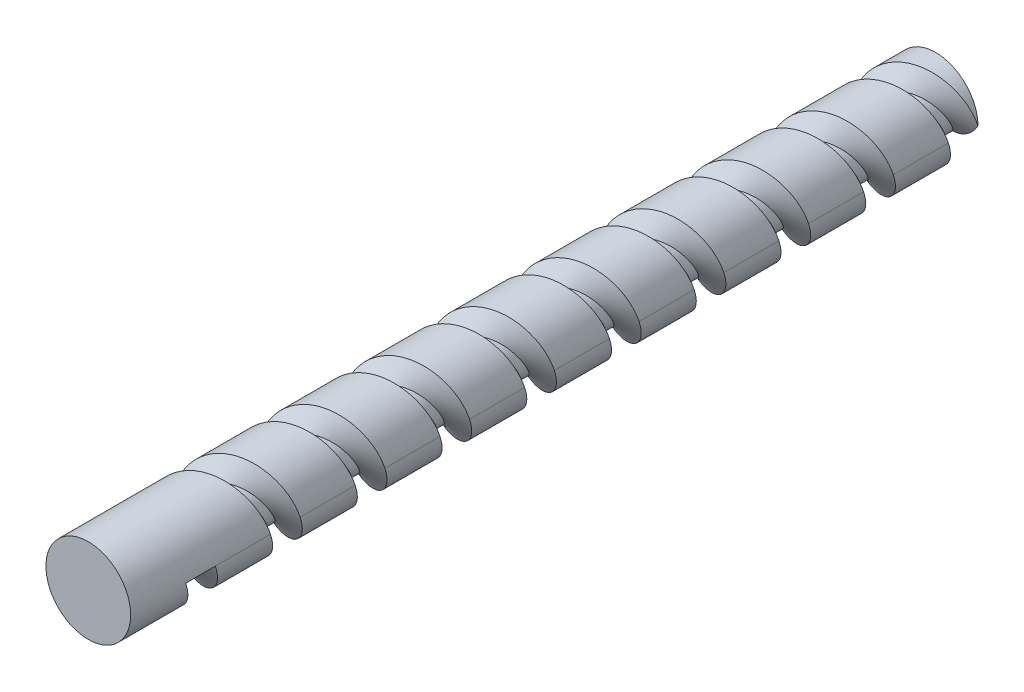
SolidWorks part; units mm, degrees
ref_plane "正面" through (0, 0, 0) normal (0, 0, 1) x (1, 0, 0)
ref_plane "平面" through (0, 0, 0) normal (0, 1, 0) x (1, 0, 0)
ref_plane "右側面" through (0, 0, 0) normal (1, 0, 0) x (0, 0, -1)
sketch "ｽｹｯﾁ1" plane through (0, 0, 0) normal (0, 0, 1) x (1, 0, 0)
  circle A0 centre (7.8709, 3.7524) radius 5
extrude "ﾎﾞｽ - 押し出し1" add sketch "ｽｹｯﾁ1" along normal blind 100
thread "ねじ山4" pitch 4 method cut profile "ねじ山の輪郭4" start angle 0, offset 10, length 100, pitch 10, diameter 10
ref_plane "平面4" through (12.8709, 3.7524, -10) normal (0, -1, 0) x (1, 0, 0)
sketch "ねじ山の輪郭4" plane through (12.8709, 3.7524, -10) normal (0, -1, 0) x (1, 0, 0)
  line L0 (0, 0) -> (0, 4) construction
  line L11 (0, 0) -> (0, 3.5)
  line L12 (0, 3.5) -> (-2.1651, 2.25)
  line L13 (-2.1651, 2.25) -> (-2.1651, 1.25)
  line L15 (-2.1651, 1.25) -> (0, 0)
  line L17 (-2.1651, 1.75) -> (0, 1.75) construction
  point P2 (0, 0)
  dimension "Pitch" = 4
  dimension "Profile_Angle" = 60
  dimension "Profile_Land" = 1
  dimension "Profile_Height" = 2.1651
